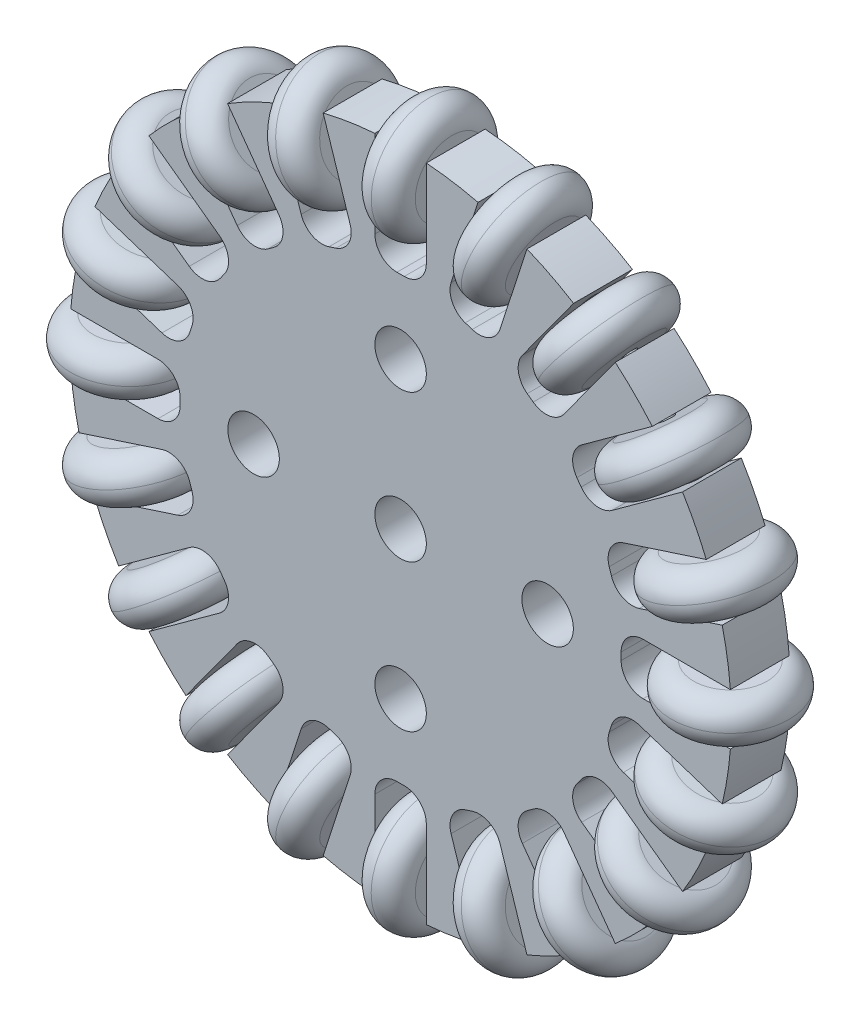
SolidWorks part; units mm, degrees
ref_plane "Front Plane" through (0, 0, 0) normal (0, 0, 1) x (1, 0, 0)
ref_plane "Top Plane" through (0, 0, 0) normal (0, 1, 0) x (1, 0, 0)
ref_plane "Right Plane" through (0, 0, 0) normal (1, 0, 0) x (0, 0, -1)
sketch "Sketch1" plane through (0, 0, 0) normal (0, 0, 1) x (1, 0, 0)
  circle A0 centre (0, 0) radius 22.5
  dimension "D1" = 45
extrude "Boss-Extrude1" add sketch "Sketch1" along normal blind 2 and the other way blind 2
sketch "Sketch2" plane through (0, 0, 2) normal (0, 0, 1) x (1, 0, 0)
  line L0 (0, 22.5) -> (0, 0) construction
  line L1 (-1.75, 30) -> (1.75, 30)
  line L2 (-1.75, 30) -> (-1.75, 16.5)
  line L3 (-0.25, 15) -> (0.25, 15)
  line L4 (1.75, 30) -> (1.75, 16.5)
  line L5 (-1.75, 30) -> (1.75, 15) construction
  line L6 (-1.75, 15) -> (1.75, 30) construction
  circle A0 centre (0, 0) radius 22.5 construction
  arc A1 (0.25, 15) -> (1.75, 16.5) centre (0.25, 16.5) ccw
  arc A2 (-1.75, 16.5) -> (-0.25, 15) centre (-0.25, 16.5) ccw
  point P0 (0, 22.5)
  dimension "D3" = 1.5
  dimension "D1" = 3.5
  dimension "D2" = 15
extrude "Cut-Extrude1" cut sketch "Sketch2" against normal through all
pattern_circular "CirPattern1" count 20 over 360 about axis through (0, 0, 2) along (0, 0, 1) of "Cut-Extrude1"
sketch "Sketch3" plane through (0, 0, 0) normal (0, 0, 1) x (1, 0, 0)
  circle A0 centre (0, 0) radius 21
  dimension "D1" = 42
sweep "Sweep1" add path "Sketch3" circular profile diameter 1 parameters "D3"=1
sketch "Sketch8" plane through (0, 0, 0) normal (1, 0, 0) x (0, 0, -1)
  line L0 (0, 22.4318) -> (0, 20.4318) construction
  line L1 (-2, 22.4318) -> (2, 22.4318) construction
  circle A0 centre (0, 20.4318) radius 4
  dimension "D2" = 8
  dimension "D1" = 2
extrude "Boss-Extrude2" add sketch "Sketch8" along normal blind 1.5 and the other way blind 1.5
fillet "Fillet1" radius 1.5 2 edges at (1.5, 20.4318, -4) (-1.5, 20.4318, -4)
pattern_circular "CirPattern3" count 20 over 360 about axis through (0, 0, 2) along (0, 0, 1) of "Boss-Extrude2", "Fillet1"
sketch "Sketch9" plane through (0, 0, -2) normal (0, 0, -1) x (-1, 0, 0)
  line L0 (-10, 0) -> (0, 0) construction
  circle A0 centre (0, 0) radius 1.75
  circle A1 centre (-10, 0) radius 1.75
  circle A2 centre (0, 10) radius 1.75
  circle A3 centre (10, 0) radius 1.75
  circle A4 centre (0, -10) radius 1.75
  point P14 (0, 0)
  dimension "D1" = 3.5
  dimension "D2" = 10
  dimension "D3" = 4
extrude "Cut-Extrude2" cut sketch "Sketch9" against normal through all
